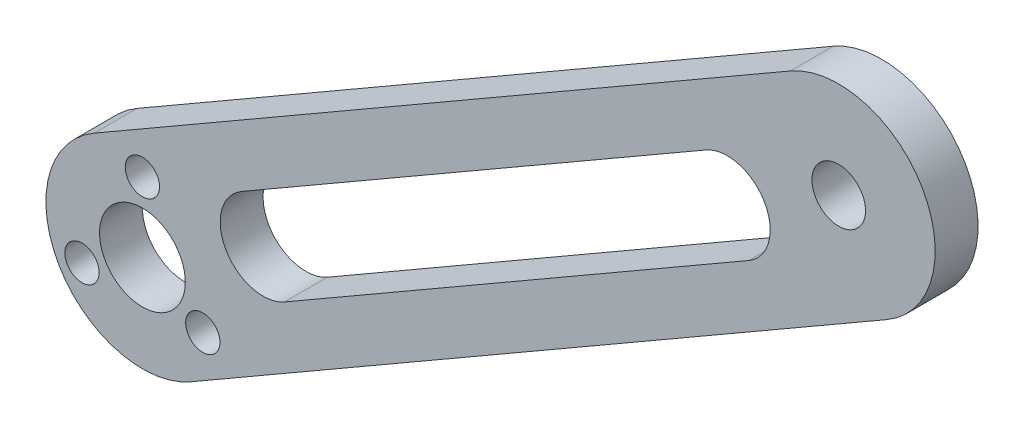
SolidWorks part; units mm, degrees
material "Thornel Mat VMA"
ref_plane "Front Plane" through (0, 0, 0) normal (0, 0, 1) x (1, 0, 0)
ref_plane "Top Plane" through (0, 0, 0) normal (0, 1, 0) x (1, 0, 0)
ref_plane "Right Plane" through (0, 0, 0) normal (1, 0, 0) x (0, 0, -1)
sketch "Sketch1" plane through (0, 0, 0) normal (0, 0, 1) x (1, 0, 0)
  line L0 (0, 0) -> (64.9519, 37.5) construction
  line L1 (0, 0) -> (51.301, 0) construction
  line L2 (60.4519, 45.2942) -> (-4.5, 7.7942)
  line L3 (4.5, -7.7942) -> (69.4519, 29.7058)
  line L4 (5.6338, -3.2527) -> (-5.6338, -3.2527) construction
  line L5 (-5.6338, -3.2527) -> (0, 6.5054) construction
  line L6 (0, 6.5054) -> (5.6338, -3.2527) construction
  circle A5 centre (0, 0) radius 4
  circle A6 centre (0, 6.5054) radius 1.6
  circle A7 centre (5.6338, -3.2527) radius 1.6
  circle A8 centre (-5.6338, -3.2527) radius 1.6
  circle A9 centre (0, 0) radius 9
  circle A10 centre (64.9519, 37.5) radius 2.5
  circle A11 centre (64.9519, 37.5) radius 9
  circle A12 centre (0, 0) radius 6.5054 construction
  dimension "D2" = 5
  dimension "D4" = 18
  dimension "D5" = 18
  dimension "D7" = 8
  dimension "D8" = 3.2
  dimension "D1" = 75
  dimension "D3" = 30
  dimension "D6" = 11.2677
extrude "Boss-Extrude1" add sketch "Sketch1" along normal blind 4 contours A9 A5 A6 A7 A8 | A11 L2 A9 L3 | A11 A10 region at (32.476, 18.75, 0) region at (69.3246, 45.0738, 0) region at (4.3727, 7.5738, 0)
sketch "Sketch2" plane through (0, 0, 4) normal (0, 0, 1) x (1, 0, 0)
  line L0 (11.2583, 6.5) -> (54.5596, 31.5) construction
  line L1 (9.2583, 9.9641) -> (52.5596, 34.9641)
  line L2 (13.2583, 3.0359) -> (56.5596, 28.0359)
  line L3 (60.4519, 45.2942) -> (-4.5, 7.7942) construction
  arc A0 (9.2583, 9.9641) -> (13.2583, 3.0359) centre (11.2583, 6.5) ccw
  arc A1 (56.5596, 28.0359) -> (52.5596, 34.9641) centre (54.5596, 31.5) ccw
  circle A2 centre (64.9519, 37.5) radius 2.5 construction
  point P2 (32.909, 19)
  dimension "D1" = 4
  dimension "D2" = 50
  dimension "D3" = 12
extrude "Cut-Extrude1" cut sketch "Sketch2" against normal blind 10
